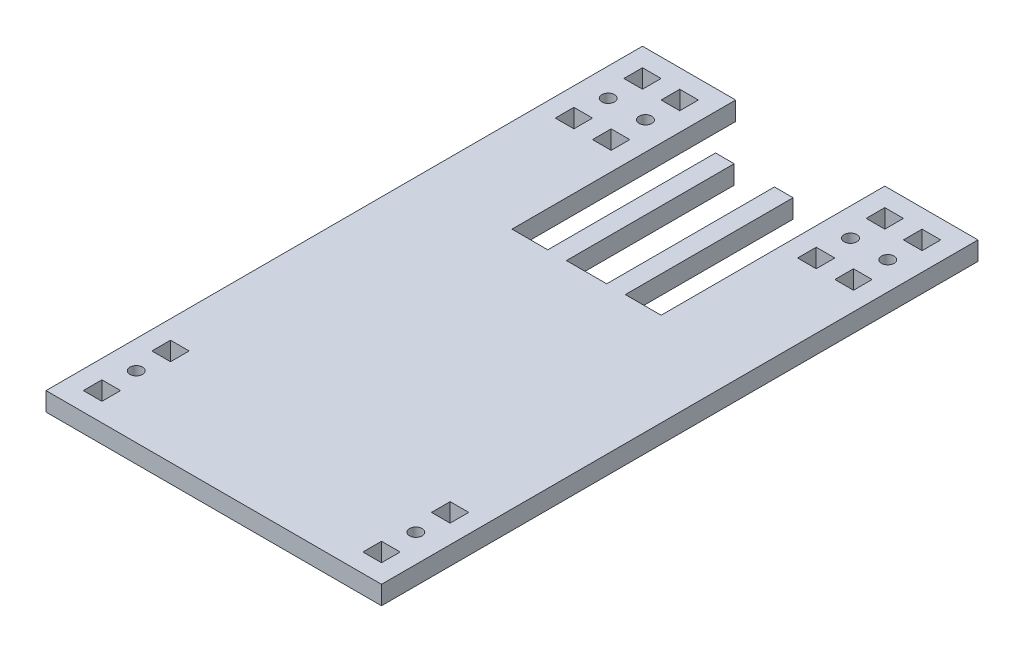
SolidWorks part; units mm, degrees
ref_plane "Front Plane" through (0, 0, 0) normal (0, 0, 1) x (1, 0, 0)
ref_plane "Top Plane" through (0, 0, 0) normal (0, 1, 0) x (1, 0, 0)
ref_plane "Right Plane" through (0, 0, 0) normal (1, 0, 0) x (0, 0, -1)
sketch "Sketch1" plane through (0, 0, 0) normal (0, 1, 0) x (1, 0, 0)
  line L0 (0, 25.4) -> (0, -101.6) construction
  line L1 (-57.15, 101.6) -> (-25.4, 101.6)
  line L2 (-57.15, 101.6) -> (-57.15, -101.6)
  line L3 (-57.15, -101.6) -> (57.15, -101.6)
  line L4 (57.15, 101.6) -> (57.15, -101.6)
  line L5 (-57.15, 101.6) -> (57.15, -101.6) construction
  line L6 (-57.15, -101.6) -> (57.15, 101.6) construction
  line L7 (-57.15, 0) -> (57.15, 0) construction
  line L8 (31.75, 101.6) -> (31.75, -101.6) construction
  line L9 (-31.75, 101.6) -> (-31.75, -101.6) construction
  line L10 (6.858, 82.55) -> (6.858, -101.6) construction
  line L11 (-6.858, 82.55) -> (-6.858, -101.6) construction
  line L12 (-6.858, 82.55) -> (-6.858, 25.4)
  line L13 (-6.858, 25.4) -> (6.858, 25.4)
  line L14 (6.858, 25.4) -> (6.858, 82.55)
  line L15 (6.858, 82.55) -> (13.208, 82.55)
  line L16 (44.45, 101.6) -> (44.45, -101.6) construction
  line L17 (-44.45, 101.6) -> (-44.45, -101.6) construction
  line L18 (13.208, 82.55) -> (13.208, 25.4)
  line L19 (13.208, 25.4) -> (25.4, 25.4)
  line L20 (25.4, 25.4) -> (25.4, 101.6)
  line L21 (25.4, 101.6) -> (57.15, 101.6)
  line L22 (-25.4, 25.4) -> (-25.4, 101.6)
  line L23 (-13.208, 25.4) -> (-25.4, 25.4)
  line L24 (-13.208, 82.55) -> (-13.208, 25.4)
  line L25 (-6.858, 25.4) -> (-6.858, 82.55)
  line L26 (-13.208, 82.55) -> (-6.858, 82.55)
  point P0 (0, 0)
  line B0 (34.925, 65.532) -> (34.925, 95.25) construction
  line B1 (32.766, 80.391) -> (37.084, 80.391) construction
  line B2 (31.75, 88.9) -> (38.1, 88.9)
  line B3 (31.75, 88.9) -> (31.75, 95.25)
  line B4 (31.75, 95.25) -> (38.1, 95.25)
  line B5 (38.1, 88.9) -> (38.1, 95.25)
  line B6 (31.75, 88.9) -> (38.1, 95.25) construction
  line B7 (31.75, 95.25) -> (38.1, 88.9) construction
  line B8 (31.75, 65.532) -> (38.1, 71.882) construction
  line B9 (31.75, 71.882) -> (38.1, 65.532) construction
  line B10 (38.1, 71.882) -> (38.1, 65.532)
  line B11 (31.75, 65.532) -> (38.1, 65.532)
  line B12 (31.75, 71.882) -> (31.75, 65.532)
  line B13 (31.75, 71.882) -> (38.1, 71.882)
  circle B14 centre (34.925, 80.391) radius 2.159
  line B15 (-34.925, 65.532) -> (-34.925, 95.25) construction
  line B16 (-32.766, 80.391) -> (-37.084, 80.391) construction
  line B17 (-31.75, 88.9) -> (-38.1, 88.9)
  line B18 (-31.75, 88.9) -> (-31.75, 95.25)
  line B19 (-31.75, 95.25) -> (-38.1, 95.25)
  line B20 (-38.1, 88.9) -> (-38.1, 95.25)
  line B21 (-31.75, 88.9) -> (-38.1, 95.25) construction
  line B22 (-31.75, 95.25) -> (-38.1, 88.9) construction
  line B23 (-31.75, 65.532) -> (-38.1, 71.882) construction
  line B24 (-31.75, 71.882) -> (-38.1, 65.532) construction
  line B25 (-38.1, 71.882) -> (-38.1, 65.532)
  line B26 (-31.75, 65.532) -> (-38.1, 65.532)
  line B27 (-31.75, 71.882) -> (-31.75, 65.532)
  line B28 (-31.75, 71.882) -> (-38.1, 71.882)
  circle B29 centre (-34.925, 80.391) radius 2.159
  line B30 (47.625, 65.532) -> (47.625, 95.25) construction
  line B31 (45.466, 80.391) -> (49.784, 80.391) construction
  line B32 (44.45, 88.9) -> (50.8, 88.9)
  line B33 (44.45, 88.9) -> (44.45, 95.25)
  line B34 (44.45, 95.25) -> (50.8, 95.25)
  line B35 (50.8, 88.9) -> (50.8, 95.25)
  line B36 (44.45, 88.9) -> (50.8, 95.25) construction
  line B37 (44.45, 95.25) -> (50.8, 88.9) construction
  line B38 (44.45, 65.532) -> (50.8, 71.882) construction
  line B39 (44.45, 71.882) -> (50.8, 65.532) construction
  line B40 (50.8, 71.882) -> (50.8, 65.532)
  line B41 (44.45, 65.532) -> (50.8, 65.532)
  line B42 (44.45, 71.882) -> (44.45, 65.532)
  line B43 (44.45, 71.882) -> (50.8, 71.882)
  circle B44 centre (47.625, 80.391) radius 2.159
  line B45 (-47.625, 65.532) -> (-47.625, 95.25) construction
  line B46 (-45.466, 80.391) -> (-49.784, 80.391) construction
  line B47 (-44.45, 88.9) -> (-50.8, 88.9)
  line B48 (-44.45, 88.9) -> (-44.45, 95.25)
  line B49 (-44.45, 95.25) -> (-50.8, 95.25)
  line B50 (-50.8, 88.9) -> (-50.8, 95.25)
  line B51 (-44.45, 88.9) -> (-50.8, 95.25) construction
  line B52 (-44.45, 95.25) -> (-50.8, 88.9) construction
  line B53 (-44.45, 65.532) -> (-50.8, 71.882) construction
  line B54 (-44.45, 71.882) -> (-50.8, 65.532) construction
  line B55 (-50.8, 71.882) -> (-50.8, 65.532)
  line B56 (-44.45, 65.532) -> (-50.8, 65.532)
  line B57 (-44.45, 71.882) -> (-44.45, 65.532)
  line B58 (-44.45, 71.882) -> (-50.8, 71.882)
  circle B59 centre (-47.625, 80.391) radius 2.159
  line B60 (47.625, -95.25) -> (47.625, -65.532) construction
  line B61 (45.466, -80.391) -> (49.784, -80.391) construction
  line B62 (44.45, -71.882) -> (50.8, -71.882)
  line B63 (44.45, -71.882) -> (44.45, -65.532)
  line B64 (44.45, -65.532) -> (50.8, -65.532)
  line B65 (50.8, -71.882) -> (50.8, -65.532)
  line B66 (44.45, -71.882) -> (50.8, -65.532) construction
  line B67 (44.45, -65.532) -> (50.8, -71.882) construction
  line B68 (44.45, -95.25) -> (50.8, -88.9) construction
  line B69 (44.45, -88.9) -> (50.8, -95.25) construction
  line B70 (50.8, -88.9) -> (50.8, -95.25)
  line B71 (44.45, -95.25) -> (50.8, -95.25)
  line B72 (44.45, -88.9) -> (44.45, -95.25)
  line B73 (44.45, -88.9) -> (50.8, -88.9)
  circle B74 centre (47.625, -80.391) radius 2.159
  line B75 (-47.625, -95.25) -> (-47.625, -65.532) construction
  line B76 (-49.784, -80.391) -> (-45.466, -80.391) construction
  line B77 (-50.8, -71.882) -> (-44.45, -71.882)
  line B78 (-50.8, -71.882) -> (-50.8, -65.532)
  line B79 (-50.8, -65.532) -> (-44.45, -65.532)
  line B80 (-44.45, -71.882) -> (-44.45, -65.532)
  line B81 (-50.8, -71.882) -> (-44.45, -65.532) construction
  line B82 (-50.8, -65.532) -> (-44.45, -71.882) construction
  line B83 (-50.8, -95.25) -> (-44.45, -88.9) construction
  line B84 (-50.8, -88.9) -> (-44.45, -95.25) construction
  line B85 (-44.45, -88.9) -> (-44.45, -95.25)
  line B86 (-50.8, -95.25) -> (-44.45, -95.25)
  line B87 (-50.8, -88.9) -> (-50.8, -95.25)
  line B88 (-50.8, -88.9) -> (-44.45, -88.9)
  circle B89 centre (-47.625, -80.391) radius 2.159
  dimension "D1" = 63.5
  dimension "D2" = 6.35
  dimension "D3" = 6.858
  dimension "D4" = 6.35
  dimension "D5" = 6.35
  dimension "D6" = 203.2
  dimension "D7" = 19.05
  dimension "D8" = 6.35
  dimension "D9" = 6.35
  dimension "D10" = 6.35
  dimension "D11" = 6.35
  dimension "D12" = 76.2
sketch_block_instance "Female T-Slot Assembly-1"
sketch_block "Female T-Slot Assembly" parameters "D4"=4.318, "D1"=6.35, "D2"=6.35, "D3"=6.35
sketch_block_instance "Female T-Slot Assembly-3"
sketch_block_instance "Female T-Slot Assembly-5"
sketch_block_instance "Female T-Slot Assembly-10"
sketch_block_instance "Female T-Slot Assembly-1"
sketch_block_instance "Female T-Slot Assembly-1"
extrude "Boss-Extrude1" add sketch "Sketch1" along normal blind 6.35 contours L26 L24 L23 L22 L1 L2 L3 L4 L21 L20 L19 L18 L15 L14 L13 L12 B89 B72 B73 B70 B71 B65 B62 B63 B64 B47 B50 B49 B48 B44 B29 B28 B27 B26 B25 B12 B13 B10 B11 B5 B2 B3 region at (0, 0, 11.3769)
equation "\"Ball Diameter\"= 1.75in"
equation "\"Ball Radius\" = \"Ball Diameter\"/2"
equation "\"Sheet Thickness\"= 0.25in"
equation "\"Screw Diameter\"= .17in"
equation "\"Robot Diameter\"= 14in"
equation "\"Castor Screw Diameter\"= 0.22in"
equation "\"Wheel Diameter\" = 4in"
equation "\"Nut Diameter\" = 8.4mm"
equation "\"Nut Height\" = 2.9mm"
equation "\"Screw Height\" = 0.55in"
equation "\"Pulley Diameter\" = 1in"
equation "\"Reactor Height\" = 14in"
equation "\"Elevator Height\" = 11.5in"
equation "\"Elevator Width\" = \"Ball Diameter\" + 0.25in"
equation "\"Elevator Bearing Diameter\" = sqr(2*(\"Sheet Thickness\"^2)) + 0.2in"
equation "\"Elevator Axle Endcap Diameter\" = \"Pulley Diameter\" + 0.25in"
equation "\"Elevator Axle Length\" = \"Elevator Width\" + 8*\"Sheet Thickness\""
equation "\"Elevator Clearance from Axis\" = 3.28in"
equation "\"Elevator Horizontal Clearance\" = \"Elevator Width\" + 0.5in"
equation "\"Claw Horizontal Seperation\" = (\"Elevator Width\"/2) - (1.5 * \"Sheet Thickness\") - 0.15in"
equation "\"Claw Radius\" = \"Ball Radius\" + 0.1in"
equation "\"Castor Wheel Height\" = 1.25in"
